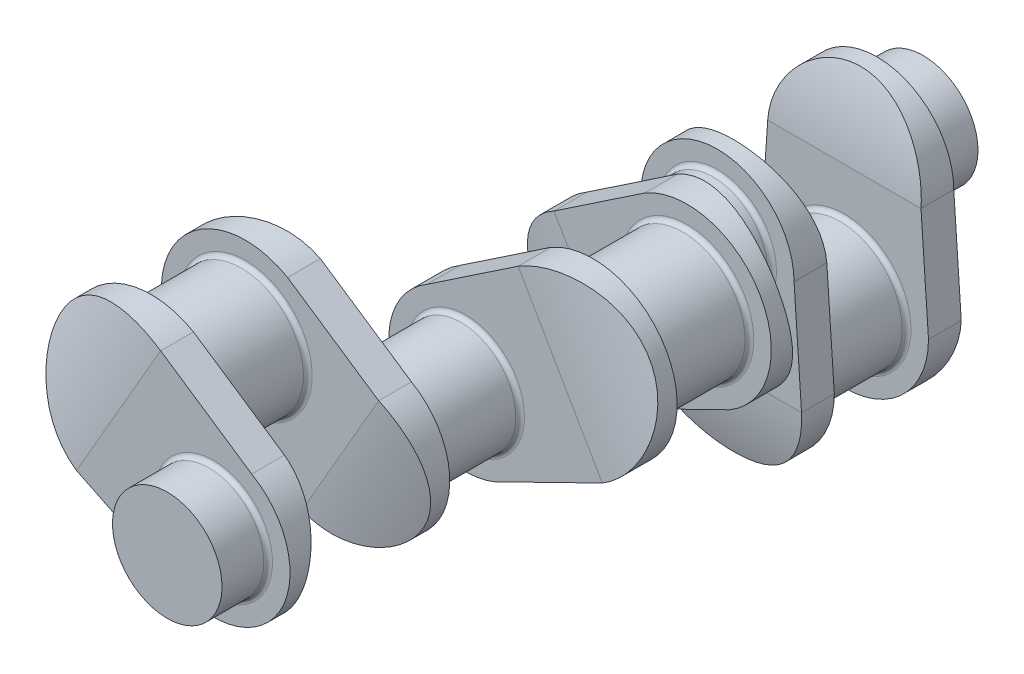
SolidWorks part; units mm, degrees
ref_plane "Front Plane" through (0, 0, 0) normal (0, 0, 1) x (1, 0, 0)
ref_plane "Top Plane" through (0, 0, 0) normal (0, 1, 0) x (1, 0, 0)
ref_plane "Right Plane" through (0, 0, 0) normal (1, 0, 0) x (0, 0, -1)
sketch "Sketch2" plane through (0, 0, 0) normal (0, 0, 1) x (1, 0, 0)
  circle A0 centre (0, 0) radius 36.1
  dimension "D1" = 72.2
extrude "Boss-Extrude1" add sketch "Sketch2" along normal blind 27.31
sketch "Sketch3" plane through (0, 0, 27.31) normal (0, 0, 1) x (1, 0, 0)
  line L0 (-44.45, 63.5) -> (-48.8, 0)
  line L1 (44.45, 63.5) -> (48.8, 0)
  arc A0 (-48.8, 0) -> (48.8, 0) centre (0, 0) ccw
  arc A1 (44.45, 63.5) -> (-44.45, 63.5) centre (0, 63.5) ccw
  circle A2 centre (0, 0) radius 36.1 construction
  point P1 (0, 0)
  dimension "D1" = 12.7
  dimension "D3" = 88.9
  dimension "D2" = 63.5
extrude "Boss-Extrude2" add sketch "Sketch3" along normal blind 19
sketch "Sketch4" plane through (0, 0, 46.31) normal (0, 0, 1) x (1, 0, 0)
  circle A0 centre (0, 63.5) radius 31.75
  dimension "D1" = 63.5
extrude "Boss-Extrude3" add sketch "Sketch4" along normal blind 26.76
sketch "Sketch5" plane through (0, 0, 0) normal (1, 0, 0) x (0, 0, -1)
  line L0 (-46.31, -48.8) -> (-27.31, -48.8) construction
  line L1 (-46.31, 0) -> (-66.0442, 0)
  line L2 (-66.0442, 0) -> (-66.0442, -48.8)
  line L3 (-66.0442, -48.8) -> (-36.81, -48.8)
  arc A0 (-46.31, 0) -> (-36.81, -48.8) centre (122.5216, 7.5421) ccw
  dimension "D1" = 169
extrude "Cut-Extrude1" cut sketch "Sketch5" against normal through all both and the other way through all
sketch "Sketch6" plane through (0, 0, 0) normal (1, 0, 0) x (0, 0, -1)
  line L0 (-27.31, 107.95) -> (-46.31, 107.95) construction
  line L4 (-36.81, 107.95) -> (-15.7351, 107.95)
  line L9 (-15.7351, 107.95) -> (-15.7351, 63.5)
  line L10 (-15.7351, 63.5) -> (-27.31, 63.5)
  arc A2 (-36.81, 107.95) -> (-27.31, 63.5) centre (-195.8264, 50.7243) cw
  dimension "D1" = 169
extrude "Cut-Extrude7" cut sketch "Sketch6" against normal through all both and the other way through all
fillet "Fillet6" radius 2.54 2 edges at (31.75, 63.5, 46.31) (36.1, 0, 27.31)
mirror "Mirror1" about plane through (0, 0, 0) normal (0, 0, 1) of "Fillet6", "Cut-Extrude7", "Cut-Extrude1", "Boss-Extrude3", "Boss-Extrude2", "Boss-Extrude1"
pattern_linear "LPattern13" count 3 spacing 146.14 along (0, 0, 1) of bodies 112
ref_axis "Axis1" through (0, 63.5, -145.407) along (0, 0, 1)
move or copy body "Body-Move/Copy1" bodies to move or copy 115 copy no rotation origin (0, 63.5, 0) rotation axis (0, 0, 1) rotation angle 120
move or copy body "Body-Move/Copy2" bodies to move or copy 116 copy no rotation origin (0, 63.5, 0) rotation axis (0, 0, -1) rotation angle 120
combine bodies "Combine1" operation type add bodies to combine 118 117 112
